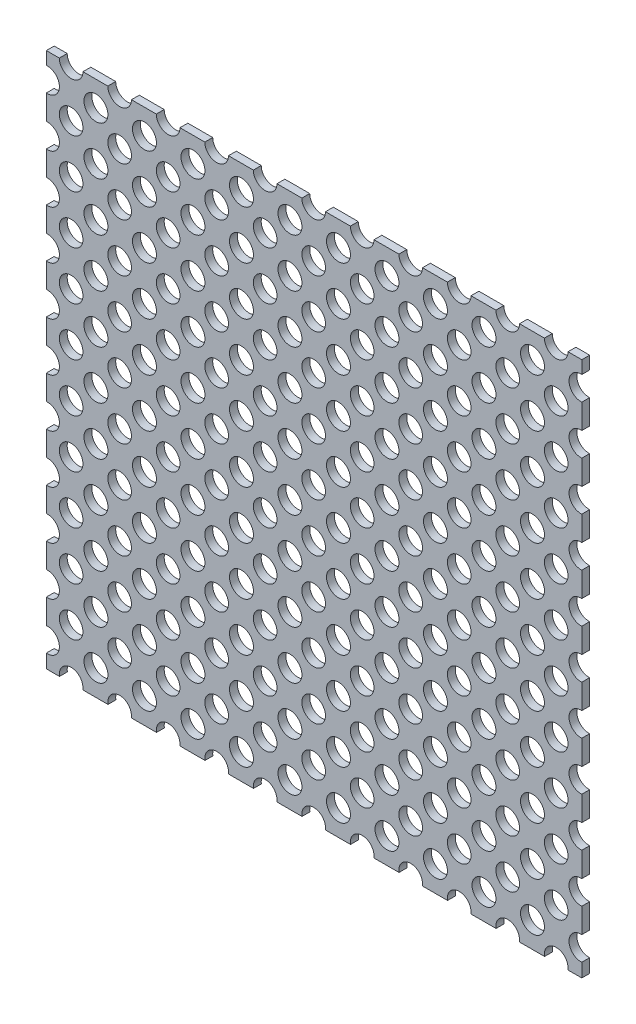
SolidWorks part; units mm, degrees
material "6061 Alloy"
ref_plane "Front Plane" through (0, 0, 0) normal (0, 0, 1) x (1, 0, 0)
ref_plane "Top Plane" through (0, 0, 0) normal (0, 1, 0) x (1, 0, 0)
ref_plane "Right Plane" through (0, 0, 0) normal (1, 0, 0) x (0, 0, -1)
sketch "Sketch1" plane through (0, 0, 0) normal (0, 0, 1) x (1, 0, 0)
  line L1 (-107.95, 107.95) -> (107.95, 107.95)
  line L2 (-107.95, 107.95) -> (-107.95, -107.95)
  line L3 (-107.95, -107.95) -> (107.95, -107.95)
  line L4 (107.95, 107.95) -> (107.95, -107.95)
  line L5 (-107.95, 107.95) -> (107.95, -107.95) construction
  line L6 (-107.95, -107.95) -> (107.95, 107.95) construction
  point P0 (0, 0)
  dimension "D1" = 215.9
  dimension "D2" = 215.9
extrude "Boss-Extrude1" add sketch "Sketch1" against normal blind 3.175
sketch "Sketch2" plane through (0, 0, 0) normal (0, 0, 1) x (1, 0, 0)
  line L0 (-107.95, 107.95) -> (-107.95, -107.95) construction
  line L2 (107.95, 107.95) -> (-107.95, 107.95) construction
  circle A0 centre (-97.95, 107.95) radius 4.7625
  circle A1 centre (-87.95, 97.95) radius 4.826
  dimension "D1" = 9.525
  dimension "D2" = 10
  dimension "D4" = 9.652
  dimension "D5" = 10
  dimension "D6" = 10
extrude "Cut-Extrude1" cut sketch "Sketch2" against normal blind 3.175
pattern_linear "LPattern1" count 16 spacing 19.558 along (1, 0, 0) count 2 spacing 19.558 along (-1, 0, 0) of "Cut-Extrude1" pattern seed only yes
pattern_linear "LPattern2" count 16 spacing 19.558 along (0, -1, 0) of "LPattern1"
